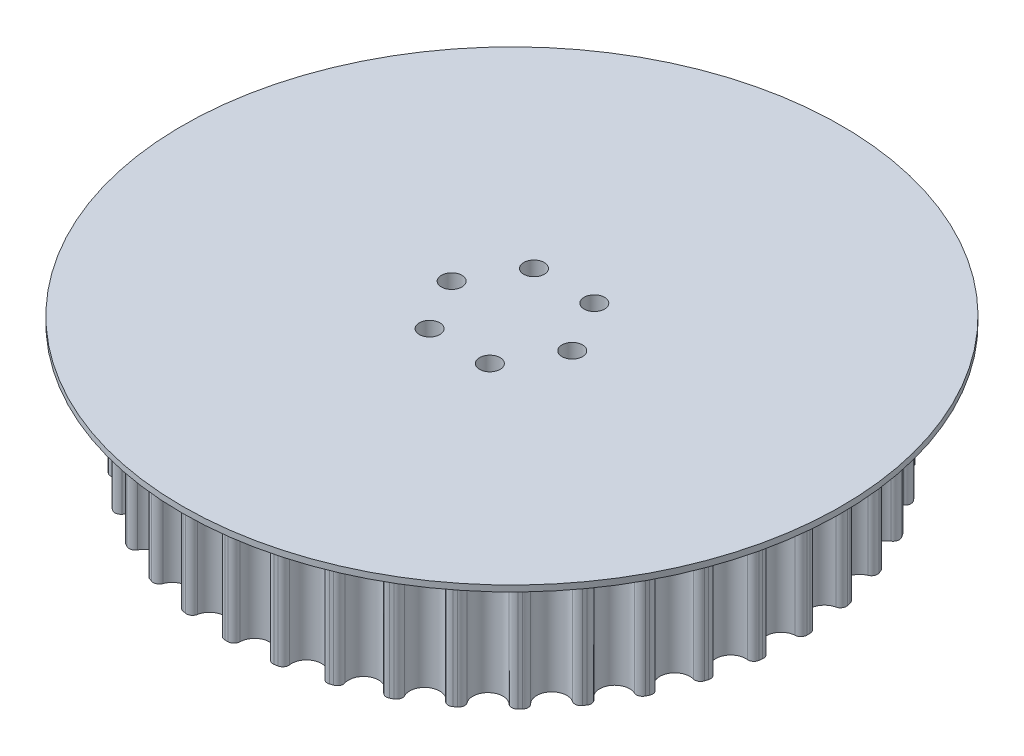
SolidWorks part; units mm, degrees
material "PETG"
ref_plane "Front Plane" through (0, 0, 0) normal (0, 0, 1) x (1, 0, 0)
ref_plane "Top Plane" through (0, 0, 0) normal (0, 1, 0) x (1, 0, 0)
ref_plane "Right Plane" through (0, 0, 0) normal (1, 0, 0) x (0, 0, -1)
sketch "Sketch5" plane through (0, 0, 0) normal (0, 1, 0) x (1, 0, 0)
  line L0 (0, 9.7022) -> (0, 50009.7022) construction
  line L1 (0, 0) -> (0, 46.5575) construction
  line L3 (0, 0) -> (-3.9957, 49.4953) construction
  line L5 (0, 0) -> (3.9957, 49.4953) construction
  circle A0 centre (0, 0) radius 49.6563 construction
  circle A2 centre (0, 0) radius 47.3449 construction
  arc A3 (-2.4772, 46.3129) -> (2.4772, 46.3129) centre (0, 46.5575) ccw
  arc A43 (3.8097, 47.1914) -> (3.5472, 47.2119) centre (0, 0) ccw
  arc A45 (-3.5472, 47.2119) -> (-3.8097, 47.1914) centre (0, 0) ccw
  arc A46 (-2.4772, 46.3129) -> (-3.5472, 47.2119) centre (-3.4723, 46.2147) ccw
  arc A47 (3.5472, 47.2119) -> (2.4772, 46.3129) centre (3.4723, 46.2147) ccw
  arc A48 (4.984, 46.1106) -> (9.8742, 45.3158) centre (7.4684, 45.9546) ccw
  arc A49 (4.984, 46.1106) -> (4.072, 47.1695) centre (3.986, 46.1732) ccw
  arc A50 (4.072, 47.1695) -> (3.8097, 47.1914) centre (0, 0) ccw
  arc A51 (11.0746, 46.0315) -> (9.8742, 45.3158) centre (10.8407, 45.0592) ccw
  arc A52 (11.3304, 45.9692) -> (11.0746, 46.0315) centre (0, 0) ccw
  arc A53 (12.3162, 44.714) -> (17.0155, 43.1451) centre (14.7433, 44.1615) ccw
  arc A54 (12.3162, 44.714) -> (11.5858, 45.9055) centre (11.3411, 44.9359) ccw
  arc A55 (11.5858, 45.9055) -> (11.3304, 45.9692) centre (0, 0) ccw
  arc A56 (18.3152, 43.6589) -> (17.0155, 43.1451) centre (17.9283, 42.7367) ccw
  arc A57 (18.5576, 43.5564) -> (18.3152, 43.6589) centre (0, 0) ccw
  arc A58 (19.3293, 42.1593) -> (23.7161, 39.8569) centre (21.6364, 41.2247) ccw
  arc A59 (19.3293, 42.1593) -> (18.7995, 43.4525) centre (18.4025, 42.5347) ccw
  arc A60 (18.7995, 43.4525) -> (18.5576, 43.5564) centre (0, 0) ccw
  arc A61 (25.0814, 40.1556) -> (23.7161, 39.8569) centre (24.5516, 39.3074) ccw
  arc A62 (25.3043, 40.0155) -> (25.0814, 40.1556) centre (0, 0) ccw
  arc A63 (25.8418, 38.5127) -> (29.8025, 35.5364) centre (27.9691, 37.2201) ccw
  arc A64 (25.8418, 38.5127) -> (25.5264, 39.8742) centre (24.9872, 39.032) ccw
  arc A65 (25.5264, 39.8742) -> (25.3043, 40.0155) centre (0, 0) ccw
  arc A66 (31.198, 35.6122) -> (29.8025, 35.5364) centre (30.539, 34.86) ccw
  arc A67 (31.3955, 35.4382) -> (31.198, 35.6122) centre (0, 0) ccw
  arc A68 (31.685, 33.8686) -> (35.117, 30.2956) centre (33.5774, 32.2515) ccw
  arc A69 (31.685, 33.8686) -> (31.5921, 35.2631) centre (30.9248, 34.5183) ccw
  arc A70 (31.5921, 35.2631) -> (31.3955, 35.4382) centre (0, 0) ccw
  arc A71 (36.5066, 30.1465) -> (35.117, 30.2956) centre (35.7355, 29.5098) ccw
  arc A72 (36.6736, 29.9431) -> (36.5066, 30.1465) centre (0, 0) ccw
  arc A73 (36.7076, 28.3474) -> (39.522, 24.2701) centre (38.3161, 26.4477) ccw
  arc A74 (36.7076, 28.3474) -> (36.8395, 29.7387) centre (36.0614, 29.1106) ccw
  arc A75 (36.8395, 29.7387) -> (36.6736, 29.9431) centre (0, 0) ccw
  arc A76 (40.8697, 23.9001) -> (39.522, 24.2701) centre (40.0064, 23.3953) ccw
  arc A77 (41.0019, 23.6725) -> (40.8697, 23.9001) centre (0, 0) ccw
  arc A78 (40.7795, 22.092) -> (42.9034, 17.616) centre (42.0624, 19.9589) ccw
  arc A79 (40.7795, 22.092) -> (41.1329, 23.4441) centre (40.2641, 22.949) ccw
  arc A80 (41.1329, 23.4441) -> (41.0019, 23.6725) centre (0, 0) ccw
  arc A81 (44.1743, 17.0346) -> (42.9034, 17.616) centre (43.2412, 16.6748) ccw
  arc A82 (44.2683, 16.7887) -> (44.1743, 17.0346) centre (0, 0) ccw
  arc A83 (43.7952, 15.2644) -> (45.1736, 10.5057) centre (44.7194, 12.9531) ccw
  arc A84 (43.7952, 15.2644) -> (44.361, 16.5424) centre (43.424, 16.193) ccw
  arc A85 (44.361, 16.5424) -> (44.2683, 16.7887) centre (0, 0) ccw
  arc A86 (46.3348, 9.728) -> (45.1736, 10.5057) centre (45.3561, 9.5225) ccw
  arc A87 (46.3881, 9.4702) -> (46.3348, 9.728) centre (0, 0) ccw
  arc A88 (45.6767, 8.0415) -> (46.2739, 3.1233) centre (46.2181, 5.6119) ccw
  arc A89 (45.6767, 8.0415) -> (46.4401, 9.2121) centre (45.4592, 9.0176) ccw
  arc A90 (46.4401, 9.2121) -> (46.3881, 9.4702) centre (0, 0) ccw
  arc A91 (47.2952, 2.1694) -> (46.2739, 3.1233) centre (46.2963, 2.1236) ccw
  arc A92 (47.3065, 1.9064) -> (47.2952, 2.1694) centre (0, 0) ccw
  arc A93 (46.3751, 0.6103) -> (46.1756, -4.34) centre (46.5198, -1.8747) ccw
  arc A94 (46.3751, 0.6103) -> (47.3164, 1.6433) centre (46.317, 1.6086) ccw
  arc A95 (47.3164, 1.6433) -> (47.3065, 1.9064) centre (0, 0) ccw
  arc A96 (47.0307, -5.4454) -> (46.1756, -4.34) centre (46.0374, -5.3304) ccw
  arc A97 (46.9997, -5.7068) -> (47.0307, -5.4454) centre (0, 0) ccw
  arc A98 (45.8725, -6.8367) -> (44.8815, -11.6909) centre (45.6166, -9.3127) ccw
  arc A99 (45.8725, -6.8367) -> (46.9673, -5.968) centre (45.9753, -5.842) ccw
  arc A100 (46.9673, -5.968) -> (46.9997, -5.7068) centre (0, 0) ccw
  arc A101 (45.5482, -12.9191) -> (44.8815, -11.6909) centre (44.5862, -12.6463) ccw
  arc A102 (45.4757, -13.1722) -> (45.5482, -12.9191) centre (0, 0) ccw
  arc A103 (44.1818, -14.1066) -> (42.4249, -18.739) centre (43.5321, -16.5095) ccw
  arc A104 (44.1818, -14.1066) -> (45.4017, -13.4248) centre (44.4428, -13.1413) ccw
  arc A105 (45.4017, -13.4248) -> (45.4757, -13.1722) centre (0, 0) ccw
  arc A106 (42.886, -20.0583) -> (42.4249, -18.739) centre (41.9802, -19.6346) ccw
  arc A107 (42.7738, -20.2964) -> (42.886, -20.0583) centre (0, 0) ccw
  arc A108 (41.3468, -21.0112) -> (38.8696, -25.3017) centre (40.32, -23.2788) ccw
  arc A109 (41.3468, -21.0112) -> (42.6603, -20.5339) centre (41.7592, -20.1002) ccw
  arc A110 (42.6603, -20.5339) -> (42.7738, -20.2964) centre (0, 0) ccw
  arc A111 (39.1131, -26.6779) -> (38.8696, -25.3017) centre (38.2869, -26.1145) ccw
  arc A112 (38.9641, -26.895) -> (39.1131, -26.6779) centre (0, 0) ccw
  arc A113 (37.4409, -27.3716) -> (34.3076, -31.2092) centre (36.0637, -29.4451) ccw
  arc A114 (37.4409, -27.3716) -> (38.814, -27.1112) centre (37.9942, -26.5386) ccw
  arc A115 (38.814, -27.1112) -> (38.9641, -26.895) centre (0, 0) ccw
  arc A116 (34.3271, -32.6066) -> (34.3076, -31.2092) centre (33.6021, -31.9179) ccw
  arc A117 (34.1453, -32.797) -> (34.3271, -32.6066) centre (0, 0) ccw
  arc A118 (32.5653, -33.0231) -> (28.857, -36.3084) centre (30.8734, -34.8488) ccw
  arc A119 (32.5653, -33.0231) -> (33.9624, -32.9863) centre (33.2451, -32.2896) ccw
  arc A120 (33.9624, -32.9863) -> (34.1453, -32.797) centre (0, 0) ccw
  arc A121 (28.6521, -37.6908) -> (28.857, -36.3084) centre (28.0469, -36.8948) ccw
  arc A122 (28.4421, -37.8496) -> (28.6521, -37.6908) centre (0, 0) ccw
  arc A123 (26.8464, -37.8193) -> (22.659, -40.4672) centre (24.8834, -39.35) ccw
  arc A124 (26.8464, -37.8193) -> (28.2312, -38.0071) centre (27.6349, -37.2044) ccw
  arc A125 (28.2312, -38.0071) -> (28.4421, -37.8496) centre (0, 0) ccw
  arc A126 (22.235, -41.7989) -> (22.659, -40.4672) centre (21.7654, -40.916) ccw
  arc A127 (22.0023, -41.9219) -> (22.235, -41.7989) centre (0, 0) ccw
  arc A128 (20.4321, -41.636) -> (15.8742, -43.5779) centre (18.249, -42.832) ccw
  arc A129 (20.4321, -41.636) -> (21.7689, -42.0436) centre (21.3091, -41.1555) ccw
  arc A130 (21.7689, -42.0436) -> (22.0023, -41.9219) centre (0, 0) ccw
  arc A131 (15.2421, -44.8243) -> (15.8742, -43.5779) centre (14.9202, -43.8776) ccw
  arc A132 (14.9926, -44.9084) -> (15.2421, -44.8243) centre (0, 0) ccw
  arc A133 (13.4886, -44.3744) -> (8.6782, -45.56) centre (11.1419, -45.2047) ccw
  arc A134 (13.4886, -44.3744) -> (14.7427, -44.9911) centre (14.4313, -44.0408) ccw
  arc A135 (14.7427, -44.9911) -> (14.9926, -44.9084) centre (0, 0) ccw
  arc A136 (7.8544, -46.6889) -> (8.6782, -45.56) centre (7.6885, -45.7027) ccw
  arc A137 (7.5947, -46.7318) -> (7.8544, -46.6889) centre (0, 0) ccw
  arc A138 (6.1958, -45.9634) -> (1.2575, -46.3621) centre (3.7463, -46.4066) ccw
  arc A139 (6.1958, -45.9634) -> (7.3347, -46.7733) centre (7.1798, -45.7854) ccw
  arc A140 (7.3347, -46.7733) -> (7.5947, -46.7318) centre (0, 0) ccw
  arc A141 (0.2632, -47.3442) -> (1.2575, -46.3621) centre (0.2577, -46.3442) ccw
  arc A142 (0, -47.3449) -> (0.2632, -47.3442) centre (0, 0) ccw
  arc A143 (-1.2575, -46.3621) -> (-6.1958, -45.9634) centre (-3.7463, -46.4066) ccw
  arc A144 (-1.2575, -46.3621) -> (-0.2632, -47.3442) centre (-0.2577, -46.3442) ccw
  arc A145 (-0.2632, -47.3442) -> (0, -47.3449) centre (0, 0) ccw
  arc A146 (-7.3347, -46.7733) -> (-6.1958, -45.9634) centre (-7.1798, -45.7854) ccw
  arc A147 (-7.5947, -46.7318) -> (-7.3347, -46.7733) centre (0, 0) ccw
  arc A148 (-8.6782, -45.56) -> (-13.4886, -44.3744) centre (-11.1419, -45.2047) ccw
  arc A149 (-8.6782, -45.56) -> (-7.8544, -46.6889) centre (-7.6885, -45.7027) ccw
  arc A150 (-7.8544, -46.6889) -> (-7.5947, -46.7318) centre (0, 0) ccw
  arc A151 (-14.7427, -44.9911) -> (-13.4886, -44.3744) centre (-14.4313, -44.0408) ccw
  arc A152 (-14.9926, -44.9084) -> (-14.7427, -44.9911) centre (0, 0) ccw
  arc A153 (-15.8742, -43.5779) -> (-20.4321, -41.636) centre (-18.249, -42.832) ccw
  arc A154 (-15.8742, -43.5779) -> (-15.2421, -44.8243) centre (-14.9202, -43.8776) ccw
  arc A155 (-15.2421, -44.8243) -> (-14.9926, -44.9084) centre (0, 0) ccw
  arc A156 (-21.7689, -42.0436) -> (-20.4321, -41.636) centre (-21.3091, -41.1555) ccw
  arc A157 (-22.0023, -41.9219) -> (-21.7689, -42.0436) centre (0, 0) ccw
  arc A158 (-22.659, -40.4672) -> (-26.8464, -37.8193) centre (-24.8834, -39.35) ccw
  arc A159 (-22.659, -40.4672) -> (-22.235, -41.7989) centre (-21.7654, -40.916) ccw
  arc A160 (-22.235, -41.7989) -> (-22.0023, -41.9219) centre (0, 0) ccw
  arc A161 (-28.2312, -38.0071) -> (-26.8464, -37.8193) centre (-27.6349, -37.2044) ccw
  arc A162 (-28.4421, -37.8496) -> (-28.2312, -38.0071) centre (0, 0) ccw
  arc A163 (-28.857, -36.3084) -> (-32.5653, -33.0231) centre (-30.8734, -34.8488) ccw
  arc A164 (-28.857, -36.3084) -> (-28.6521, -37.6908) centre (-28.0469, -36.8948) ccw
  arc A165 (-28.6521, -37.6908) -> (-28.4421, -37.8496) centre (0, 0) ccw
  arc A166 (-33.9624, -32.9863) -> (-32.5653, -33.0231) centre (-33.2451, -32.2896) ccw
  arc A167 (-34.1453, -32.797) -> (-33.9624, -32.9863) centre (0, 0) ccw
  arc A168 (-34.3076, -31.2092) -> (-37.4409, -27.3716) centre (-36.0637, -29.4451) ccw
  arc A169 (-34.3076, -31.2092) -> (-34.3271, -32.6066) centre (-33.6021, -31.9179) ccw
  arc A170 (-34.3271, -32.6066) -> (-34.1453, -32.797) centre (0, 0) ccw
  arc A171 (-38.814, -27.1112) -> (-37.4409, -27.3716) centre (-37.9942, -26.5386) ccw
  arc A172 (-38.9641, -26.895) -> (-38.814, -27.1112) centre (0, 0) ccw
  arc A173 (-38.8696, -25.3017) -> (-41.3468, -21.0112) centre (-40.32, -23.2788) ccw
  arc A174 (-38.8696, -25.3017) -> (-39.1131, -26.6779) centre (-38.2869, -26.1145) ccw
  arc A175 (-39.1131, -26.6779) -> (-38.9641, -26.895) centre (0, 0) ccw
  arc A176 (-42.6603, -20.5339) -> (-41.3468, -21.0112) centre (-41.7592, -20.1002) ccw
  arc A177 (-42.7738, -20.2964) -> (-42.6603, -20.5339) centre (0, 0) ccw
  arc A178 (-42.4249, -18.739) -> (-44.1818, -14.1066) centre (-43.5321, -16.5095) ccw
  arc A179 (-42.4249, -18.739) -> (-42.886, -20.0583) centre (-41.9802, -19.6346) ccw
  arc A180 (-42.886, -20.0583) -> (-42.7738, -20.2964) centre (0, 0) ccw
  arc A181 (-45.4017, -13.4248) -> (-44.1818, -14.1066) centre (-44.4428, -13.1413) ccw
  arc A182 (-45.4757, -13.1722) -> (-45.4017, -13.4248) centre (0, 0) ccw
  arc A183 (-44.8815, -11.6909) -> (-45.8725, -6.8367) centre (-45.6166, -9.3127) ccw
  arc A184 (-44.8815, -11.6909) -> (-45.5482, -12.9191) centre (-44.5862, -12.6463) ccw
  arc A185 (-45.5482, -12.9191) -> (-45.4757, -13.1722) centre (0, 0) ccw
  arc A186 (-46.9673, -5.968) -> (-45.8725, -6.8367) centre (-45.9753, -5.842) ccw
  arc A187 (-46.9997, -5.7068) -> (-46.9673, -5.968) centre (0, 0) ccw
  arc A188 (-46.1756, -4.34) -> (-46.3751, 0.6103) centre (-46.5198, -1.8747) ccw
  arc A189 (-46.1756, -4.34) -> (-47.0307, -5.4454) centre (-46.0374, -5.3304) ccw
  arc A190 (-47.0307, -5.4454) -> (-46.9997, -5.7068) centre (0, 0) ccw
  arc A191 (-47.3164, 1.6433) -> (-46.3751, 0.6103) centre (-46.317, 1.6086) ccw
  arc A192 (-47.3065, 1.9064) -> (-47.3164, 1.6433) centre (0, 0) ccw
  arc A193 (-46.2739, 3.1233) -> (-45.6767, 8.0415) centre (-46.2181, 5.6119) ccw
  arc A194 (-46.2739, 3.1233) -> (-47.2952, 2.1694) centre (-46.2963, 2.1236) ccw
  arc A195 (-47.2952, 2.1694) -> (-47.3065, 1.9064) centre (0, 0) ccw
  arc A196 (-46.4401, 9.2121) -> (-45.6767, 8.0415) centre (-45.4592, 9.0176) ccw
  arc A197 (-46.3881, 9.4702) -> (-46.4401, 9.2121) centre (0, 0) ccw
  arc A198 (-45.1736, 10.5057) -> (-43.7952, 15.2644) centre (-44.7194, 12.9531) ccw
  arc A199 (-45.1736, 10.5057) -> (-46.3348, 9.728) centre (-45.3561, 9.5225) ccw
  arc A200 (-46.3348, 9.728) -> (-46.3881, 9.4702) centre (0, 0) ccw
  arc A201 (-44.361, 16.5424) -> (-43.7952, 15.2644) centre (-43.424, 16.193) ccw
  arc A202 (-44.2683, 16.7887) -> (-44.361, 16.5424) centre (0, 0) ccw
  arc A203 (-42.9034, 17.616) -> (-40.7795, 22.092) centre (-42.0624, 19.9589) ccw
  arc A204 (-42.9034, 17.616) -> (-44.1743, 17.0346) centre (-43.2412, 16.6748) ccw
  arc A205 (-44.1743, 17.0346) -> (-44.2683, 16.7887) centre (0, 0) ccw
  arc A206 (-41.1329, 23.4441) -> (-40.7795, 22.092) centre (-40.2641, 22.949) ccw
  arc A207 (-41.0019, 23.6725) -> (-41.1329, 23.4441) centre (0, 0) ccw
  arc A208 (-39.522, 24.2701) -> (-36.7076, 28.3474) centre (-38.3161, 26.4477) ccw
  arc A209 (-39.522, 24.2701) -> (-40.8697, 23.9001) centre (-40.0064, 23.3953) ccw
  arc A210 (-40.8697, 23.9001) -> (-41.0019, 23.6725) centre (0, 0) ccw
  arc A211 (-36.8395, 29.7387) -> (-36.7076, 28.3474) centre (-36.0614, 29.1106) ccw
  arc A212 (-36.6736, 29.9431) -> (-36.8395, 29.7387) centre (0, 0) ccw
  arc A213 (-35.117, 30.2956) -> (-31.685, 33.8686) centre (-33.5774, 32.2515) ccw
  arc A214 (-35.117, 30.2956) -> (-36.5066, 30.1465) centre (-35.7355, 29.5098) ccw
  arc A215 (-36.5066, 30.1465) -> (-36.6736, 29.9431) centre (0, 0) ccw
  arc A216 (-31.5921, 35.2631) -> (-31.685, 33.8686) centre (-30.9248, 34.5183) ccw
  arc A217 (-31.3955, 35.4382) -> (-31.5921, 35.2631) centre (0, 0) ccw
  arc A218 (-29.8025, 35.5364) -> (-25.8418, 38.5127) centre (-27.9691, 37.2201) ccw
  arc A219 (-29.8025, 35.5364) -> (-31.198, 35.6122) centre (-30.539, 34.86) ccw
  arc A220 (-31.198, 35.6122) -> (-31.3955, 35.4382) centre (0, 0) ccw
  arc A221 (-25.5264, 39.8742) -> (-25.8418, 38.5127) centre (-24.9872, 39.032) ccw
  arc A222 (-25.3043, 40.0155) -> (-25.5264, 39.8742) centre (0, 0) ccw
  arc A223 (-23.7161, 39.8569) -> (-19.3293, 42.1593) centre (-21.6364, 41.2247) ccw
  arc A224 (-23.7161, 39.8569) -> (-25.0814, 40.1556) centre (-24.5516, 39.3074) ccw
  arc A225 (-25.0814, 40.1556) -> (-25.3043, 40.0155) centre (0, 0) ccw
  arc A226 (-18.7995, 43.4525) -> (-19.3293, 42.1593) centre (-18.4025, 42.5347) ccw
  arc A227 (-18.5576, 43.5564) -> (-18.7995, 43.4525) centre (0, 0) ccw
  arc A228 (-17.0155, 43.1451) -> (-12.3162, 44.714) centre (-14.7433, 44.1615) ccw
  arc A229 (-17.0155, 43.1451) -> (-18.3152, 43.6589) centre (-17.9283, 42.7367) ccw
  arc A230 (-18.3152, 43.6589) -> (-18.5576, 43.5564) centre (0, 0) ccw
  arc A231 (-11.5858, 45.9055) -> (-12.3162, 44.714) centre (-11.3411, 44.9359) ccw
  arc A232 (-11.3304, 45.9692) -> (-11.5858, 45.9055) centre (0, 0) ccw
  arc A233 (-9.8742, 45.3158) -> (-4.984, 46.1106) centre (-7.4684, 45.9546) ccw
  arc A234 (-9.8742, 45.3158) -> (-11.0746, 46.0315) centre (-10.8407, 45.0592) ccw
  arc A235 (-11.0746, 46.0315) -> (-11.3304, 45.9692) centre (0, 0) ccw
  arc A236 (-4.072, 47.1695) -> (-4.984, 46.1106) centre (-3.986, 46.1732) ccw
  arc A237 (-3.8097, 47.1914) -> (-4.072, 47.1695) centre (0, 0) ccw
  point P9 (0, 44.0683)
  point P14 (0, 49.6563)
  point P31 (0, 47.3449)
  dimension "D3" = 2.4892
  dimension "D4" = 99.3127
  dimension "D6" = 1
  dimension "D2" = 5.588
  dimension "D1" = 3.2766
  dimension "D5" = 8
  dimension "D7" = 39
extrude "Boss-Extrude3" add sketch "Sketch5" along normal mid plane 22 contours A2 | A45 A237 A236 A233 A234 A235 A232 A231 A228 A229 A230 A227 A226 A223 A224 A225 A222 A221 A218 A219 A220 A217 A216 A213 A214 A215 A212 A211 A208 A209 A210 A207 A206 A203 A204 A205 A202 A201 A198 A199 A200 A197 A196 region at (0, 0, 0)
sketch "Sketch2" plane through (0, 11, 0) normal (0, 1, 0) x (1, 0, 0)
  circle A0 centre (0, 0) radius 54.6563
  dimension "D1" = 109.3127
extrude "Boss-Extrude2" add sketch "Sketch2" along normal blind 1
sketch "Sketch3" plane through (0, 12, 0) normal (0, 1, 0) x (1, 0, 0)
  line L0 (0, 0) -> (10, 0) construction
  circle A0 centre (10, 0) radius 1.7
  circle A1 centre (5, -8.6603) radius 1.7
  circle A2 centre (-5, -8.6603) radius 1.7
  circle A3 centre (-10, 0) radius 1.7
  circle A4 centre (-5, 8.6603) radius 1.7
  circle A5 centre (5, 8.6603) radius 1.7
  dimension "D1" = 10
  dimension "D2" = 3.4
  dimension "D3" = 6
extrude "Cut-Extrude1" cut sketch "Sketch3" against normal through all
sketch "Sketch4" plane through (0, -11, 0) normal (0, 1, 0) x (1, 0, 0)
  line L0 (0, 0) -> (5, -8.6603) construction
  circle A0 centre (5, -8.6603) radius 3
  circle A1 centre (-5, -8.6603) radius 3
  circle A2 centre (-10, 0) radius 3
  circle A3 centre (-5, 8.6603) radius 3
  circle A4 centre (5, 8.6603) radius 3
  circle A5 centre (10, 0) radius 3
  dimension "D1" = 6
  dimension "D2" = 6
extrude "Cut-Extrude2" cut sketch "Sketch4" along normal offset from surface (13 mm away) 10 up to face at (10, 12, 1.7)
sketch "Sketch6" plane through (0, -11, 0) normal (0, -1, 0) x (1, 0, 0)
  line L0 (0, 0) -> (35, 0) construction
  circle A0 centre (35, 0) radius 2
  circle A1 centre (-17.5, -30.3109) radius 2
  circle A2 centre (-17.5, 30.3109) radius 2
  dimension "D2" = 4
  dimension "D1" = 35
  dimension "D3" = 3
extrude "Cut-Extrude3" cut sketch "Sketch6" against normal blind 20
equation "\"pitch\"= 8mm"
equation "\"n\"= 39"
equation "\"pitch_dia\"= \"pitch\" * \"n\" / PI"
equation "\"belt_width\"= 22mm"
equation "\"D1@Sketch2\"=\"pitch_dia\"+10.00mm"
equation "\"D4@Sketch5\"=\"pitch_dia\""
equation "\"D1@Boss-Extrude3\" = \"belt_width\""
equation "\"D7@Sketch5\"=\"n\""
equation "\"D5@Sketch5\"=\"pitch\""
equation "\"tol_dia_id_intfc\" = 0.0500mm ' For hole diameters - Interference fit"
equation "\"tol_dia_id_slip\"  = 0.0750mm ' For hole diameters - Slip fit"
equation "\"tol_dia_id_clear\" = 0.1000mm ' For hole diameters - Clearance fit"
equation "\"tol_dia_od_intfc\" = 0.0500mm ' For shaft diameters - Interference fit"
equation "\"tol_dia_od_slip\"  = 0.0750mm ' For shaft diameters - Slip fit"
equation "\"tol_dia_od_clear\" = 0.1000mm ' For shaft diameters - Clearance fit"
equation "\"tol_general_intfc\"= 0.0250mm ' For general parts (Horiz) - Interference fit"
equation "\"tol_general_slip\" = 0.0375mm ' For general parts (Horiz) - Slip fit"
equation "\"tol_general_clear\"= 0.0500mm ' For general parts (Horiz) - Clearance fit"
equation "\"tol_layer_intfc\"  = 0.0250mm ' For all parts (Vert) - Interference fit"
equation "\"tol_layer_slip\"   = 0.0375mm ' For all parts (Vert) - Slip fit"
equation "\"tol_layer_clear\"  = 0.0500mm ' For all parts (Vert) - Clearance fit"
equation "\"tol_corner_rad\"   = 0.100mm ' For corners that fit into other parts"
equation "\"D2@Sketch6\"=3.95+\"tol_dia_id_intfc\""
